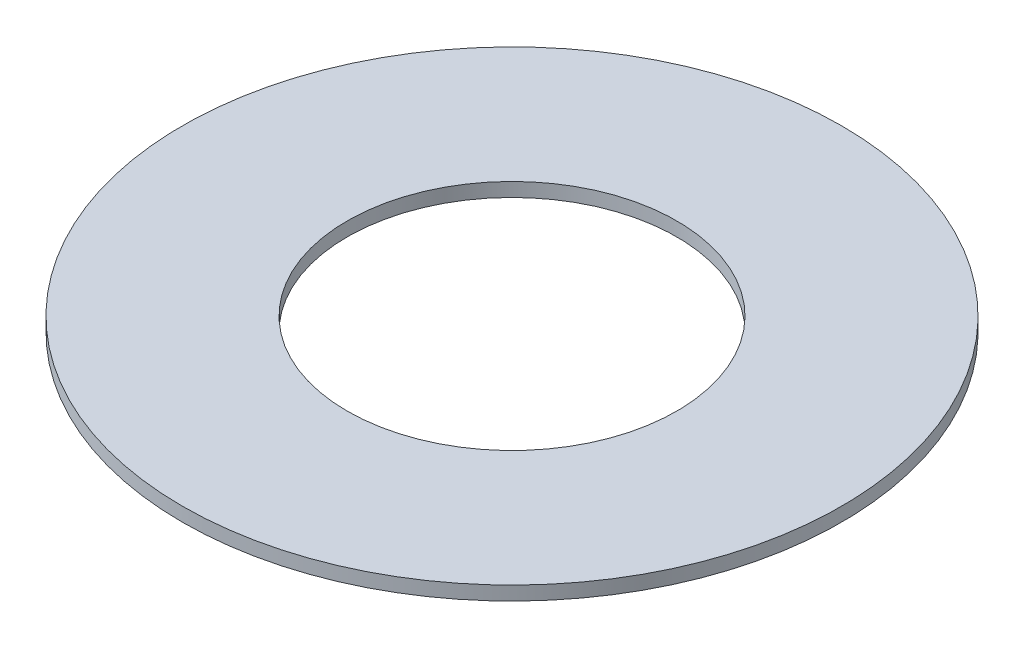
SolidWorks part; units mm, degrees
ref_plane "Front Plane" through (0, 0, 0) normal (0, 0, 1) x (1, 0, 0)
ref_plane "Top Plane" through (0, 0, 0) normal (0, 1, 0) x (1, 0, 0)
ref_plane "Right Plane" through (0, 0, 0) normal (1, 0, 0) x (0, 0, -1)
sketch "Sketch1" plane through (0, 0, 0) normal (0, 1, 0) x (1, 0, 0)
  circle A0 centre (0, 0) radius 95
  dimension "FLANGE_OD" = 190
extrude "Boss-Extrude1" add sketch "Sketch1" along normal blind 4
sketch "Sketch2" plane through (0, 0, 0) normal (0, 1, 0) x (1, 0, 0)
  circle A0 centre (0, 0) radius 47.5
  dimension "BORE_D" = 95
extrude "Cut-Extrude1" cut sketch "Sketch2" along normal through all
sketch "Sketch3" plane through (0, 4, 0) normal (0, 1, 0) x (1, 0, 0)
  circle A0 centre (0, 0) radius 41.4542 construction
  circle A1 centre (-41.4542, 0) radius 4.8198
  dimension "BOLT_D" = 9.6395
  dimension "BOLT_PCD" = 82.9084
extrude "Cut-Extrude2" cut sketch "Sketch3" against normal blind 3.0908 rebuild error yes
pattern_circular "CirPattern1" count 8 over 360 rebuild error yes
